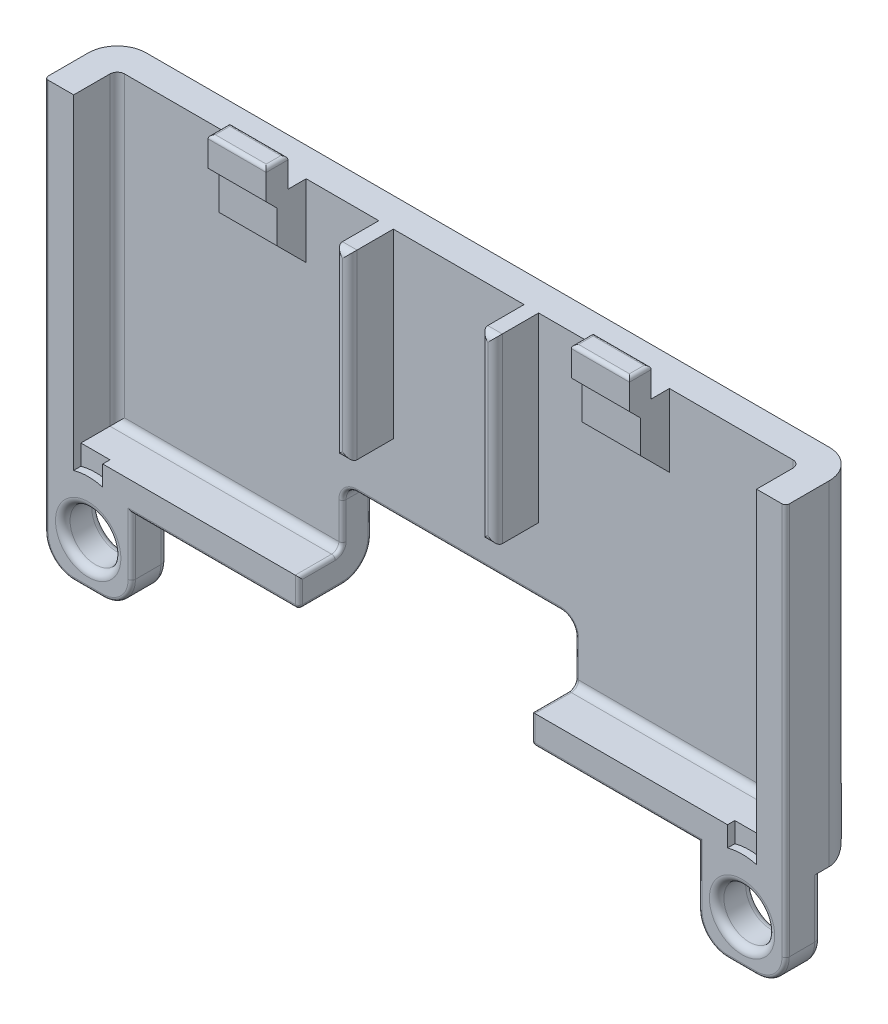
SolidWorks part; units mm, degrees
ref_plane "Alzado" through (0, 0, 0) normal (0, 0, 1) x (1, 0, 0)
ref_plane "Planta" through (0, 0, 0) normal (0, 1, 0) x (1, 0, 0)
ref_plane "Vista lateral" through (0, 0, 0) normal (1, 0, 0) x (0, 0, -1)
sketch "Croquis1" plane through (0, 0, 0) normal (0, 0, 1) x (1, 0, 0)
  line L0 (23.5, -8.3134) -> (23.5, 12.6866) construction
  line L1 (23.5, 12.6866) -> (-23.5, 12.6866) construction
  line L2 (-23.5, -8.3134) -> (23.5, -8.3134) construction
  line L3 (-23.5, 12.6866) -> (-23.5, -8.3134) construction
  line L4 (-25.5, 12.6866) -> (-25.5, -14.3134)
  line L5 (-23.5, -16.3134) -> (-21.5, -16.3134)
  line L6 (-19.5, -14.3134) -> (-19.5, -10.3134)
  line L7 (-19.5, -10.3134) -> (19.5, -10.3134)
  line L8 (19.5, -10.3134) -> (19.5, -14.3134)
  line L9 (21.5, -16.3134) -> (23.5, -16.3134)
  line L10 (25.5, -14.3134) -> (25.5, 12.6866)
  line L11 (23.5, 14.6866) -> (-23.5, 14.6866)
  circle A0 centre (-22.5, -13.3134) radius 1.75
  circle A1 centre (22.5, -13.3134) radius 1.75
  arc A2 (-25.5, -14.3134) -> (-23.5, -16.3134) centre (-23.5, -14.3134) ccw
  arc A3 (-21.5, -16.3134) -> (-19.5, -14.3134) centre (-21.5, -14.3134) ccw
  arc A4 (19.5, -14.3134) -> (21.5, -16.3134) centre (21.5, -14.3134) ccw
  arc A5 (23.5, -16.3134) -> (25.5, -14.3134) centre (23.5, -14.3134) ccw
  arc A6 (25.5, 12.6866) -> (23.5, 14.6866) centre (23.5, 12.6866) ccw
  arc A7 (-23.5, 14.6866) -> (-25.5, 12.6866) centre (-23.5, 12.6866) ccw
  point P27 (0, 12.6866)
  point P30 (-22.5, -16.3134)
  point P32 (22.5, -16.3134)
  dimension "D1" = 51
extrude "Saliente-Extruir1" add sketch "Croquis1" against normal blind 5
sketch "Croquis2" plane through (0, 0, -5) normal (0, 0, -1) x (-1, 0, 0)
  line L0 (-25.5, -14.3134) -> (-25.5, 12.6866) construction
  line L1 (-25.5, -10.3134) -> (25.7355, -10.3134)
  line L2 (-25.5, -10.3134) -> (-25.5, -17.4022)
  line L3 (-25.5, -17.4022) -> (25.7355, -17.4022)
  line L4 (25.7355, -10.3134) -> (25.7355, -17.4022)
extrude "Cortar-Extruir1" cut sketch "Croquis2" against normal blind 2.5
fillet "Redondeo2" radius 2 6 edges at (25.5, 1.1866, -5) (24.9142, 14.1008, -5) (-25.5, 1.1866, -5) (-24.9142, 14.1008, -5) (0, -10.3134, -5) (0, 14.6866, -5)
shell "Vaciado1" thickness 2 removed face at (24.25, -13.3134, 0)
sketch "Croquis3" plane through (0, 0, -5) normal (0, 0, -1) x (-1, 0, 0)
  line L0 (25.5, -10.3134) -> (-25.5, -10.3134) construction
  line L1 (-8, -16.3134) -> (8, -16.3134)
  line L2 (-8, -16.3134) -> (-8, -4.3134)
  line L3 (-8, -4.3134) -> (8, -4.3134)
  line L4 (8, -16.3134) -> (8, -4.3134)
  line L5 (-8, -16.3134) -> (8, -4.3134) construction
  line L6 (-8, -4.3134) -> (8, -16.3134) construction
  line L8 (-25.5, -10.3134) -> (-25.5, 12.6866) construction
  line L9 (25.5, 12.6866) -> (25.5, -10.3134) construction
  point P0 (0, -10.3134)
  point P7 (-8, -10.3134)
  dimension "D1" = 17.5
  dimension "D2" = 6
  dimension "D3" = 17.5
extrude "Cortar-Extruir2" cut sketch "Croquis3" against normal blind 5
fillet "Redondeo3" radius 1 2 edges at (8, -4.3134, -4) (-8, -4.3134, -4)
sketch "Croquis4" plane through (25.5, 0, 0) normal (1, 0, 0) x (0, 0, -1)
  line L0 (0, 12.6866) -> (3, 12.6866)
  line L2 (3, 12.6866) -> (5, 12.6866)
  line L3 (5, 12.6866) -> (5, -8.3134) construction
  line L4 (5, 12.6866) -> (5, 16.3062)
  line L5 (5, 16.3062) -> (0, 16.3062)
  line L6 (0, 16.3062) -> (0, 12.6866)
  line L7 (3, 12.6866) -> (0, 12.6866) construction
  line L8 (3, -10.3134) -> (3, 12.6866) construction
extrude "Cortar-Extruir3" cut sketch "Croquis4" against normal blind 62
sketch "Croquis5" plane through (0, 0, -3) normal (0, 0, 1) x (1, 0, 0)
  line L0 (23.5, 12.6866) -> (-23.5, 12.6866) construction
  line L1 (-5.5, 12.6866) -> (-4.5, 12.6866)
  line L2 (-5.5, 12.6866) -> (-5.5, 0.1866)
  line L3 (-5.5, 0.1866) -> (-4.5, 0.1866)
  line L4 (-4.5, 12.6866) -> (-4.5, 0.1866)
  line L5 (-4.5, 0.1866) -> (4.5, 0.1866) construction
  line L6 (4.5, 12.6866) -> (5.5, 12.6866)
  line L7 (4.5, 12.6866) -> (4.5, 0.1866)
  line L8 (4.5, 0.1866) -> (5.5, 0.1866)
  line L9 (5.5, 12.6866) -> (5.5, 0.1866)
  point P12 (0, 0.1866)
  dimension "D1" = 9
  dimension "D2" = 1
  dimension "D3" = 1
  dimension "D4" = 12.5
extrude "Saliente-Extruir2" add sketch "Croquis5" along normal up to surface (3 mm away) up to face at (-20.0833, -7.7688, 0)
sketch "Croquis6" plane through (0, 0, -3) normal (0, 0, 1) x (1, 0, 0)
  line L0 (10.5, 14.6866) -> (-10.5, 14.6866) construction
  line L1 (-14.5, 9.6866) -> (-10.5, 9.6866)
  line L2 (-14.5, 9.6866) -> (-14.5, 14.6866)
  line L3 (-14.5, 14.6866) -> (-10.5, 14.6866)
  line L4 (-10.5, 9.6866) -> (-10.5, 14.6866)
  line L5 (10.5, 9.6866) -> (14.5, 9.6866)
  line L6 (10.5, 9.6866) -> (10.5, 14.6866)
  line L7 (10.5, 14.6866) -> (14.5, 14.6866)
  line L8 (14.5, 9.6866) -> (14.5, 14.6866)
  line L9 (-5.5, 12.6866) -> (-23.5, 12.6866) construction
  point P8 (0, 14.6866)
  dimension "D1" = 21
  dimension "D2" = 4
  dimension "D3" = 4
  dimension "D4" = 2
  dimension "D5" = 5
extrude "Saliente-Extruir3" add sketch "Croquis6" along normal blind 3
sketch "Croquis7" plane through (0, 14.6866, 0) normal (0, 1, 0) x (1, 0, 0)
  line L0 (-10.5, 0) -> (-10.5, 3) construction
  line L1 (-14.5, 3) -> (-10.5, 3)
  line L2 (-14.5, 3) -> (-14.5, 1.75)
  line L3 (-14.5, 1.75) -> (-10.5, 1.75)
  line L4 (-10.5, 3) -> (-10.5, 1.75)
  line L5 (10.5, 0) -> (10.5, 3) construction
  line L6 (14.5, 3) -> (10.5, 3)
  line L7 (14.5, 3) -> (14.5, 1.75)
  line L8 (14.5, 1.75) -> (10.5, 1.75)
  line L9 (10.5, 3) -> (10.5, 1.75)
  line L11 (14.5, 0) -> (10.5, 0)
  line L12 (14.5, 0) -> (14.5, 0.25)
  line L13 (14.5, 0.25) -> (10.5, 0.25)
  line L14 (10.5, 0) -> (10.5, 0.25)
  line L15 (-14.5, 0) -> (-10.5, 0)
  line L16 (-14.5, 0) -> (-14.5, 0.25)
  line L17 (-14.5, 0.25) -> (-10.5, 0.25)
  line L18 (-10.5, 0) -> (-10.5, 0.25)
  dimension "D1" = 1.25
  dimension "D2" = 0.25
extrude "Cortar-Extruir4" cut sketch "Croquis7" against normal up to surface (2 mm away) up to face at (0, 12.6866, -2.1286)
sketch "Croquis8" plane through (0, 0, 0) normal (0, 0, 1) x (1, 0, 0)
  line L0 (14.5, 9.6866) -> (14.5, 12.6866) construction
  line L1 (14.5, 12.6866) -> (10.5, 12.6866) construction
  line L2 (10.5, 12.6866) -> (10.5, 9.6866) construction
  line L3 (10.5, 9.6866) -> (14.5, 9.6866) construction
  line L4 (-10.5, 9.6866) -> (-10.5, 12.6866) construction
  line L5 (-10.5, 12.6866) -> (-14.5, 12.6866) construction
  line L6 (-14.5, 12.6866) -> (-14.5, 9.6866) construction
  line L7 (-14.5, 9.6866) -> (-10.5, 9.6866) construction
  line L8 (14.5, 9.6866) -> (14.5, 12.6866)
  line L9 (14.5, 12.6866) -> (10.5, 12.6866)
  line L10 (10.5, 12.6866) -> (10.5, 9.6866)
  line L11 (10.5, 9.6866) -> (14.5, 9.6866)
  line L12 (-10.5, 9.6866) -> (-10.5, 12.6866)
  line L13 (-10.5, 12.6866) -> (-14.5, 12.6866)
  line L14 (-14.5, 12.6866) -> (-14.5, 9.6866)
  line L15 (-14.5, 9.6866) -> (-10.5, 9.6866)
extrude "Cortar-Extruir5" cut sketch "Croquis8" against normal blind 1
chamfer "Chaflán1" distance 2 angle 45 2 edges at (12.5, 9.6866, -3) (-12.5, 9.6866, -3)
fillet "Redondeo4" radius 0.5 14 edges at (-25.5, -12.3134, -2.5) (-24.9142, -15.7276, -2.5) (-22.5, -16.3134, -2.5) (-19.5, -12.3134, -2.5) (19.5, -12.3134, -2.5) (20.0858, -15.7276, -2.5) (22.5, -16.3134, -2.5) (25.5, -12.3134, -2.5) (-20.75, -13.3134, 0) (24.25, -13.3134, 0) (20.75, -13.3134, -2.5) (-24.25, -13.3134, -2.5) (-20.0858, -15.7276, -2.5) (24.9142, -15.7276, -2.5)
fillet "Redondeo5" radius 0.25 12 edges at (-19.5, -12.3134, 0) (-20.0858, -15.7276, 0) (-22.5, -16.3134, 0) (-24.9142, -15.7276, 0) (19.5, -12.3134, 0) (20.0858, -15.7276, 0) (22.5, -16.3134, 0) (24.9142, -15.7276, 0) (13.75, -10.3134, 0) (-13.75, -10.3134, 0) (-25.5, -0.8134, 0) (25.5, -0.8134, 0)
fillet "Redondeo6" radius 0.5 12 edges at (23.5, 2.1866, -3) (15.75, -8.3134, -3) (-23.5, 2.1866, -3) (-15.75, -8.3134, -3) (-4.5, 6.4366, 0) (-5, 0.1866, 0) (-5.5, 6.4366, 0) (-5, 12.6866, 0) (5.5, 6.4366, 0) (5, 0.1866, 0) (4.5, 6.4366, 0) (5, 12.6866, 0)
chamfer "Chaflán2" distance 0.75 angle 45 2 edges at (12.5, 12.6866, -1) (-12.5, 12.6866, -1)
fillet "Redondeo7" radius 0.25 30 edges at (8, -8.3134, -1.25) (8, -8.167, -2.8536) (8, -6.5634, -3) (7.7071, -4.6063, -3) (-8, -8.3134, -1.25) (-8, -8.167, -2.8536) (-8, -6.5634, -3) (-7.7071, -4.6063, -3) (-8, -9.1884, 0) (-8, -10.2402, -0.0732) (-8, -10.3134, -1.625) (-8, -9.7276, -4.4142) (-8, -6.8134, -5) (-7.7071, -4.6063, -5) (8, -9.1884, 0) (8, -10.2402, -0.0732) (8, -10.3134, -1.625) (8, -9.7276, -4.4142) (8, -6.8134, -5) (7.7071, -4.6063, -5) (0, -4.3134, -3) (0, -4.3134, -5) (-12.5, 14.6866, -1.75) (-10.5, 14.6866, -1) (-12.5, 14.6866, -0.25) (-14.5, 14.6866, -1) (12.5, 14.6866, -0.25) (10.5, 14.6866, -1) (12.5, 14.6866, -1.75) (14.5, 14.6866, -1)
